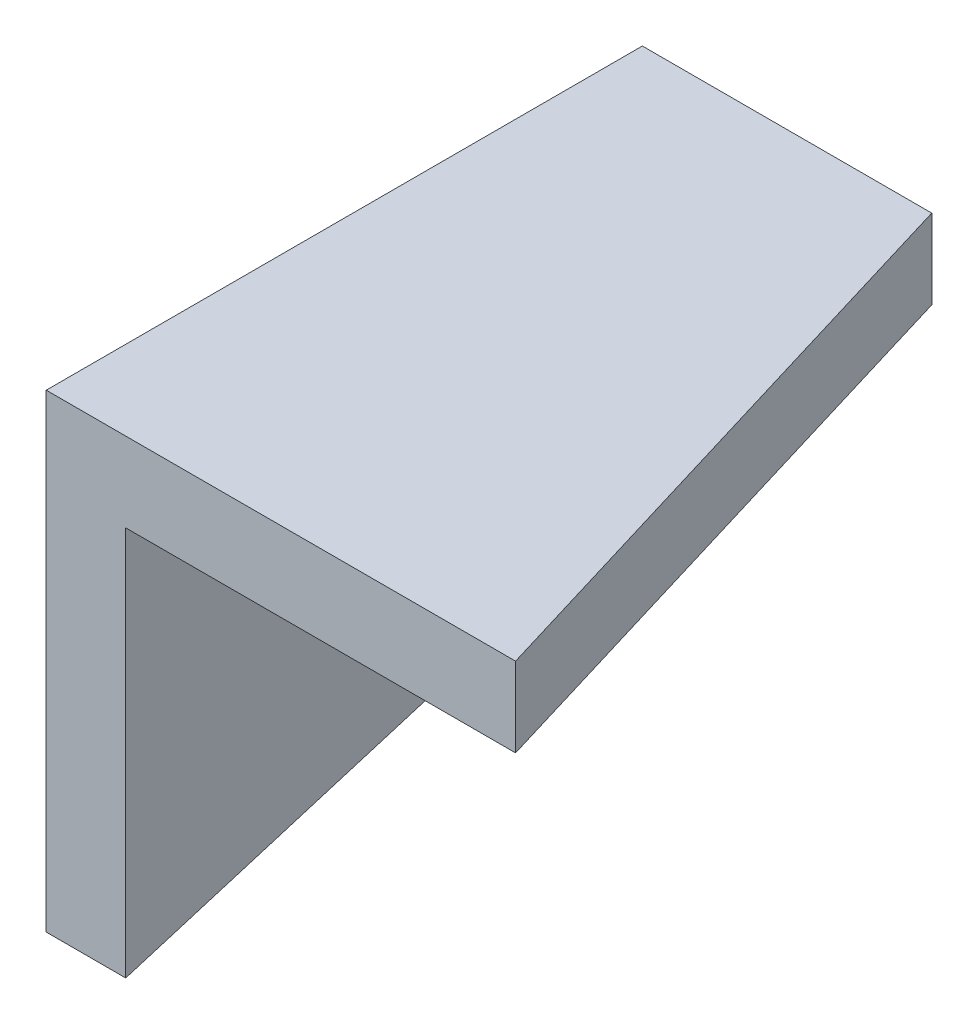
SolidWorks part; units mm, degrees
material "PLA"
ref_plane "Front Plane" through (0, 0, 0) normal (0, 0, 1) x (1, 0, 0)
ref_plane "Top Plane" through (0, 0, 0) normal (0, 1, 0) x (1, 0, 0)
ref_plane "Right Plane" through (0, 0, 0) normal (1, 0, 0) x (0, 0, -1)
sketch "Sketch1" plane through (0, 0, 0) normal (0, 0, 1) x (1, 0, 0)
  line L0 (40, 0) -> (0, 0)
  line L1 (0, 0) -> (0, -40)
  line L2 (40, 8) -> (-8, 8)
  line L3 (-8, 8) -> (-8, -40)
  line L4 (40, 0) -> (40, 8)
  line L5 (0, -40) -> (-8, -40)
  dimension "D1" = 40
  dimension "D2" = 40
  dimension "D3" = 8
extrude "Boss-Extrude1" add sketch "Sketch1" along normal mid plane 60
sketch "Sketch2" plane through (0, 0, 0) normal (0, -1, 0) x (1, 0, 0)
  line L0 (39.2402, 30) -> (21.1294, -30)
  line L1 (0, 30) -> (40, 30) construction
  line L2 (175.2248, 480.5068) -> (3.175, -89.4815) construction
  line L3 (0, -30) -> (40, -30) construction
  line L4 (21.1294, -30) -> (40, -30)
  line L5 (40, -30) -> (40, 30)
  line L6 (40, 30) -> (39.2402, 30)
extrude "Cut-Extrude1" cut sketch "Sketch2" against normal blind 10
sketch "Sketch3" plane through (0, 0, 0) normal (1, 0, 0) x (0, 0, -1)
  line L0 (30, 0) -> (30, -21.13) construction
  line L1 (30, -40) -> (30, 0) construction
  line L2 (30, -21.13) -> (-30, -39.24)
  line L3 (-30, -40) -> (-30, 0) construction
  line L4 (-30, -39.24) -> (-30, -40)
  line L5 (-30, -40) -> (30, -40)
  line L6 (30, -40) -> (30, -21.13)
  dimension "D1" = 21.13
  dimension "D2" = 39.24
extrude "Cut-Extrude2" cut sketch "Sketch3" against normal blind 10
